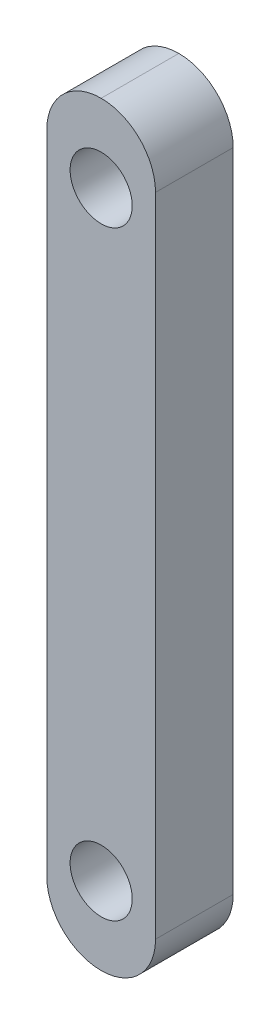
SolidWorks part; units mm, degrees
ref_plane "Front Plane" through (0, 0, 0) normal (0, 0, 1) x (1, 0, 0)
ref_plane "Top Plane" through (0, 0, 0) normal (0, 1, 0) x (1, 0, 0)
ref_plane "Right Plane" through (0, 0, 0) normal (1, 0, 0) x (0, 0, -1)
sketch "Sketch1" plane through (0, 0, 0) normal (0, 0, 1) x (1, 0, 0)
  line L0 (0, -24.32) -> (0, -19.32)
  line L1 (-3.5, 24.32) -> (3.5, 24.32)
  line L2 (-3.5, 24.32) -> (-3.5, -24.32)
  line L3 (-3.5, -24.32) -> (3.5, -24.32)
  line L4 (3.5, 24.32) -> (3.5, -24.32)
  line L5 (-3.5, 24.32) -> (3.5, -24.32) construction
  line L6 (-3.5, -24.32) -> (3.5, 24.32) construction
  line L7 (0, -19.32) -> (0, 19.32)
  line L8 (0, 19.32) -> (0, 24.32)
  circle A0 centre (0, -19.32) radius 2
  circle A1 centre (0, 19.32) radius 2
  point P0 (0, 0)
  dimension "D4" = 4
  dimension "D5" = 4
  dimension "D1" = 38.64
  dimension "D2" = 5
  dimension "D3" = 48.64
  dimension "D6" = 7
extrude "Boss-Extrude1" add sketch "Sketch1" along normal blind 5 contours A1 L7 A0 L0 L3 L4 L1 L8 | A1 L8 L1 L2 L3 L0 A0 L7 region at (-1.8218, 0, 0) region at (1.8218, 0, 0)
fillet "Fillet1" radius 3.5 4 edges at (-3.5, 24.32, 2.5) (3.5, 24.32, 2.5) (-3.5, -24.32, 2.5) (3.5, -24.32, 2.5)
